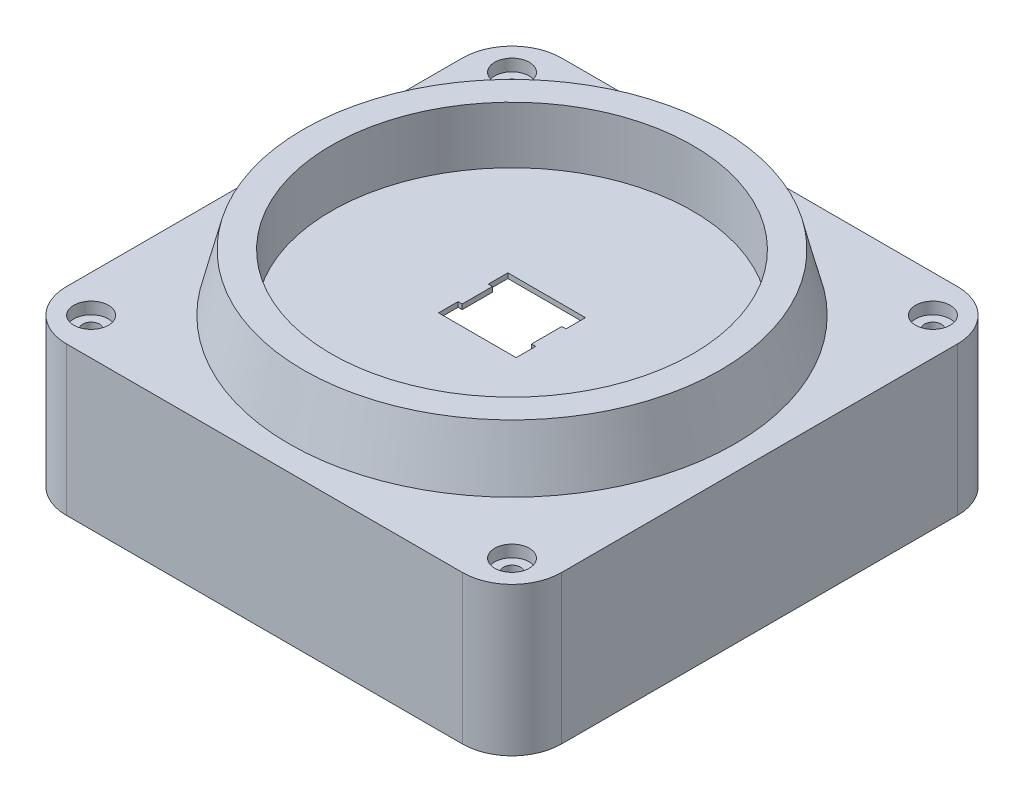
SolidWorks part; units mm, degrees
ref_plane "Ebene vorne" through (0, 0, 0) normal (0, 0, 1) x (1, 0, 0)
ref_plane "Ebene oben" through (0, 0, 0) normal (0, 1, 0) x (1, 0, 0)
ref_plane "Ebene rechts" through (0, 0, 0) normal (1, 0, 0) x (0, 0, -1)
sketch "Skizze1" plane through (0, 0, 0) normal (0, 1, 0) x (1, 0, 0)
  line L0 (-35, 47) -> (35, 47)
  line L1 (-50, -50) -> (50, -50)
  line L2 (-50, -50) -> (-50, 35)
  line L3 (-50, 50) -> (50, 50)
  line L4 (50, -50) -> (50, 50)
  line L5 (-50, -50) -> (50, 50) construction
  line L6 (-50, 50) -> (50, -50) construction
  line L7 (-50, 50) -> (-35, 50)
  line L8 (-50, 50) -> (-50, 35)
  line L9 (-47, 35) -> (-35, 35)
  line L10 (-35, 47) -> (-35, 35)
  line L11 (47, -35) -> (47, 35)
  line L12 (-35, -47) -> (35, -47)
  line L13 (-47, -35) -> (-47, 35)
  line L14 (-47, 47) -> (47, 47) construction
  line L15 (-47, -47) -> (-47, 47) construction
  line L16 (-50, -50) -> (-50, 50) construction
  line L17 (-50, 50) -> (50, 50) construction
  line L18 (0, -50) -> (0, 50) construction
  line L19 (-50, 0) -> (50, 0) construction
  line L20 (47, 35) -> (35, 35)
  line L21 (35, 47) -> (35, 35)
  line L22 (35, -47) -> (35, -35)
  line L23 (47, -35) -> (35, -35)
  line L24 (-35, -47) -> (-35, -35)
  line L25 (-47, -35) -> (-35, -35)
  line L26 (47, -47) -> (47, 47) construction
  line L27 (-47, -47) -> (47, -47) construction
  line L28 (-6.9977, -3.0607) -> (-7.8359, -3.0607)
  line L29 (-6.9977, -6.9977) -> (6.9977, -6.9977)
  line L30 (-6.9977, -3.0607) -> (-6.9977, 3.0607)
  line L31 (-6.9977, 6.9977) -> (6.9977, 6.9977)
  line L32 (6.9977, -3.0607) -> (6.9977, 3.0607)
  line L33 (-6.9977, -6.9977) -> (6.9977, 6.9977) construction
  line L34 (-6.9977, 6.9977) -> (6.9977, -6.9977) construction
  line L35 (6.9977, -6.9977) -> (7.8359, -6.9977)
  line L37 (6.9977, -3.0607) -> (7.8359, -3.0607)
  line L38 (7.8359, -6.9977) -> (7.8359, -3.0607)
  line L39 (-7.8359, -6.9977) -> (-7.8359, -3.0607)
  line L40 (-6.9977, 3.0607) -> (-7.8359, 3.0607)
  line L41 (-7.8359, 6.9977) -> (-7.8359, 3.0607)
  line L42 (6.9977, 3.0607) -> (7.8359, 3.0607)
  line L43 (7.8359, 6.9977) -> (7.8359, 3.0607)
  line L44 (7.8359, 6.9977) -> (6.9977, 6.9977)
  line L45 (-6.9977, -6.9977) -> (-7.8359, -6.9977)
  line L46 (-6.9977, 6.9977) -> (-7.8359, 6.9977)
  circle A0 centre (-42.5, 42.5) radius 1.5
  circle A1 centre (42.5, 42.5) radius 1.5
  circle A2 centre (42.5, -42.5) radius 1.5
  circle A3 centre (-42.5, -42.5) radius 1.5
  point P0 (0, 0)
  point P9 (-42.5, 42.5)
  point P24 (0, 0)
  dimension "D4" = 3
  dimension "D5" = 13.9954
  dimension "D1" = 100
  dimension "D2" = 100
  dimension "D3" = 15
  dimension "D6" = 13.9954
  dimension "D7" = 0.8382
  dimension "D8" = 3.937
extrude "Aufsatz-Linear austragen1" add sketch "Skizze1" against normal blind 30 contours L3 L8 L2 L1 L4 A1 A0 L25 L13 L9 L10 L0 L21 L20 L11 L23 L22 L12 L24 A2 A3 region at (-48.5858, 0, 7.5)
extrude "Aufsatz-Linear austragen2" add sketch "Skizze1<3>" against normal blind 1 contours L13 L25 L24 L12 L22 L23 L11 L20 L21 L0 L10 L9 region at (0, 0, -45.6706)
sketch "Skizze1<3>" plane through (0, 0, 0) normal (0, 1, 0) x (1, 0, 0) same geometry as "Skizze1"
fillet "Verrundung1" radius 10 4 edges at (50, -15, 50) (50, -15, -50) (-50, -15, -50) (-50, -15, 50)
fillet "Verrundung2" radius 12 4 edges at (35, -15.5, 35) (-35, -15.5, 35) (35, -15.5, -35) (-35, -15.5, -35)
hole_wizard "Stirnsenkung für M3 Flachkopfschraube mit Schlitz1" positions "Skizze5" profile "Skizze4" counterbore size "M3" standard "DIN" end condition through all
sketch "Skizze5" plane through (0, 0, 0) normal (0, 1, 0) x (1, 0, 0)
  point P0 (-42.5, -42.5)
  point P3 (-42.5, 42.5)
  point P6 (42.5, -42.5)
  point P9 (42.5, 42.5)
sketch "Skizze4" plane through (-42.5, 0, 42.5) normal (1, 0, 0) x (0, 0, 1)
  line L0 (0, 0) -> (0, 30)
  line L1 (0, 30) -> (1.7, 30)
  line L3 (1.7, 30) -> (1.7, 2.4)
  line L4 (1.7, 2.4) -> (3.5, 2.4)
  line L5 (3.5, 2.4) -> (3.5, 0)
  line L7 (3.5, 0) -> (0, 0)
  line L11 (0, -6.35) -> (0, 107.95) construction
  dimension "Bohrerdurchmesser" = 3.4
  dimension "Bohrungstiefe" = 30
  dimension "Senkdurchmesser2" = 7
  dimension "Senktiefe2" = 2.4
sketch "Skizze9" plane through (0, 0, 0) normal (0, 0, 1) x (1, 0, 0)
  line L0 (45.0094, 0) -> (42.1206, 11.4708)
  line L1 (-40, 0) -> (40, 0) construction
  line L2 (42.1206, 11.4708) -> (36.4839, 11.4708)
  line L3 (36.4839, 11.4708) -> (36.4839, 0)
  line L4 (36.4839, 0) -> (45.0094, 0)
  line L5 (0, -1000) -> (0, 49000) construction
revolve "Rotation1" add sketch "Skizze9" angle 360 about L5
